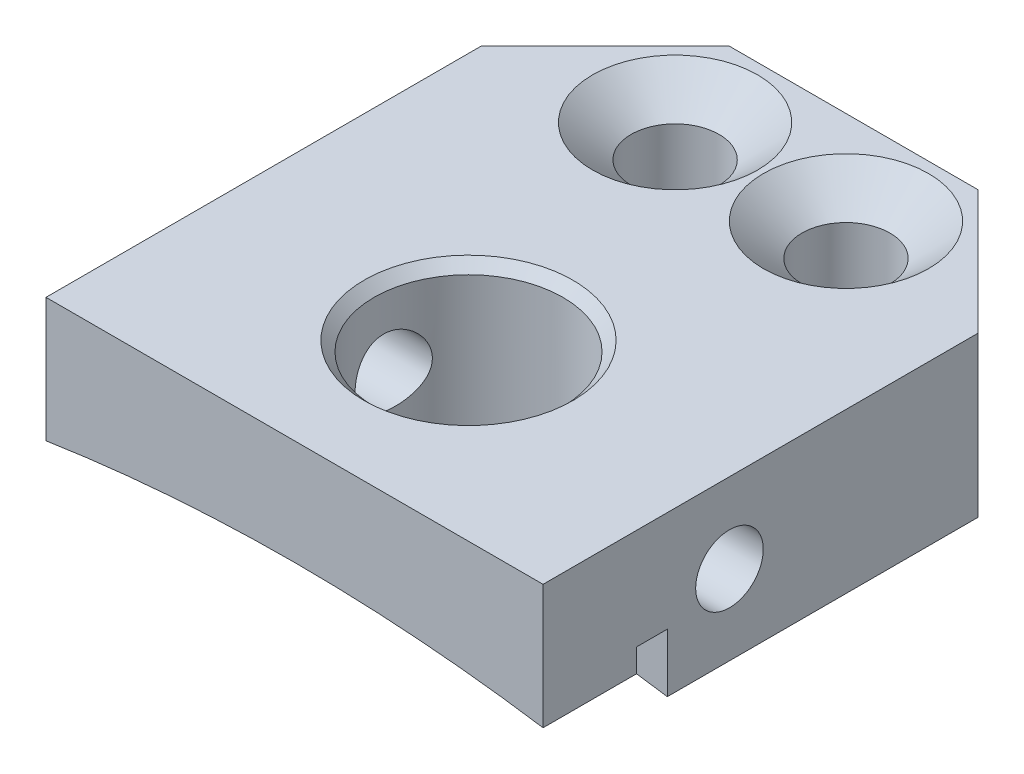
SolidWorks part; units mm, degrees
ref_plane "Front Plane" through (0, 0, 0) normal (0, 0, 1) x (1, 0, 0)
ref_plane "Top Plane" through (0, 0, 0) normal (0, 1, 0) x (1, 0, 0)
ref_plane "Right Plane" through (0, 0, 0) normal (1, 0, 0) x (0, 0, -1)
sketch "Sketch1" plane through (0, 0, 0) normal (0, 1, 0) x (1, 0, 0)
  line L0 (-28.5118, 9.6703) -> (-22.1618, 16.0203)
  line L1 (-22.1618, 16.0203) -> (-9.4618, 16.0203)
  line L2 (-28.5118, 9.6703) -> (-28.5118, -12.5547)
  line L3 (-28.5118, -12.5547) -> (-3.1118, -12.5547)
  line L4 (-3.1118, 9.6703) -> (-3.1118, -12.5547)
  line L5 (-9.4618, 16.0203) -> (-3.1118, 9.6703)
  line L6 (-15.8118, -12.5547) -> (-15.8118, 16.0203) construction
  line L8 (-3.1118, 9.6703) -> (-3.1118, 16.0203) construction
  line L9 (-3.1118, 16.0203) -> (-9.4618, 16.0203) construction
  dimension "D1" = 12.7
  dimension "D2" = 28.575
  dimension "D3" = 25.4
extrude "Boss-Extrude1" add sketch "Sketch1" along normal blind 6.35
sketch "Sketch2" plane through (0, 0, 12.5547) normal (0, 0, 1) x (1, 0, 0)
  circle A0 centre (-15.8118, -82.8523) radius 83.82
  dimension "D1" = 167.64
extrude "Cut-Extrude1" cut sketch "Sketch2" against normal through all both and the other way through all
sketch "Sketch5" plane through (0, 0, -16.0203) normal (0, 0, -1) x (-1, 0, 0)
  line L0 (3.1118, 6.35) -> (3.1118, 0) construction
  line L1 (3.1118, 6.35) -> (3.1118, 0)
  line L4 (28.5118, 6.35) -> (28.5118, 0) construction
  line L5 (28.5118, 6.35) -> (28.5118, 0)
  line L6 (28.5118, -1.7992) -> (28.5118, 0)
  line L7 (3.1118, -1.7992) -> (3.1118, 0)
  line L8 (3.1118, 6.35) -> (28.5118, 6.35)
  arc A0 (3.1118, -1.7992) -> (28.5118, -1.7992) centre (15.8118, -82.8523) cw
  arc A1 (28.5118, 0) -> (3.1118, 0) centre (15.8118, -82.8523) ccw construction
  arc A2 (28.5118, 0) -> (3.1118, 0) centre (15.8118, -82.8523) ccw construction
  dimension "D1" = 82.042
extrude "Boss-Extrude2" add sketch "Sketch5" against normal blind 22.225
chamfer "Chamfer1" distance 6.35 angle 45 2 edges at (-28.5118, 2.2754, -16.0203) (-3.1118, 2.2754, -16.0203)
hole_wizard "CSK for #8 Flat Head Machine Screw (100)1" positions "Sketch3" profile "Sketch4" countersink size "#8" standard "ANSI Inch" end condition through all
sketch "Sketch3" plane through (0, 6.35, 0) normal (0, 1, 0) x (1, 0, 0)
  line L0 (-15.8118, 16.0203) -> (-15.8118, 3.4006) construction
  line L1 (-9.4618, 16.0203) -> (-22.1618, 16.0203) construction
  point P0 (-20.1775, 11.2578)
  point P12 (-11.4462, 11.2578)
  dimension "D1" = 4.7625
  dimension "D2" = 4.3656
sketch "Sketch4" plane through (-20.1775, 6.35, -11.2578) normal (1, 0, 0) x (0, 0, 1)
  line L0 (0, 0) -> (0, 8.1492)
  line L1 (0, 8.1492) -> (2.2479, 8.1492)
  line L2 (2.2479, 8.1492) -> (2.2479, 1.6518)
  line L3 (2.2479, 1.6518) -> (4.2164, 0)
  line L5 (4.2164, 0) -> (0, 0)
  line L6 (-2.2479, 1.6518) -> (-4.2164, 0) construction
  line L11 (0, -6.35) -> (0, 107.95) construction
  dimension "Thru Hole Dia." = 4.4958
  dimension "Thru Hole Depth" = 8.1492
  dimension "Near C'Sink Dia." = 8.4328
  dimension "Near C'Sink Angle" = 100
sketch "Sketch6" plane through (0, 6.35, 0) normal (0, 1, 0) x (1, 0, 0)
  line L0 (-9.4618, 16.0203) -> (-22.1618, 16.0203) construction
  line L1 (-15.8118, -12.5547) -> (-15.8118, 16.0203) construction
  line L2 (-28.5118, -12.5547) -> (-3.1118, -12.5547) construction
  circle A1 centre (-15.8118, -3.6647) radius 1.524
  dimension "D1" = 3.048
  dimension "D2" = 19.685
extrude "Cut-Extrude2" cut sketch "Sketch6" against normal through all
sketch "Sketch7" plane through (-3.1118, 0, 0) normal (1, 0, 0) x (0, 0, -1)
  line L1 (-6.2047, -1.7992) -> (-7.7922, -1.7992)
  line L2 (-6.2047, -1.7992) -> (-6.2047, 1.1906)
  line L3 (-6.2047, 1.1906) -> (-7.7922, 1.1906)
  line L4 (-7.7922, -1.7992) -> (-7.7922, 1.1906)
  line L5 (-6.2047, -1.7992) -> (9.6703, -1.7992) construction
  line L6 (-12.5547, 0) -> (-6.2047, 0) construction
  line L7 (-6.2047, 0) -> (-6.2047, -1.7992) construction
  dimension "D1" = 1.5875
  dimension "D2" = 1.1906
extrude "Cut-Extrude3" cut sketch "Sketch7" against normal through all
sketch "Sketch8" plane through (0, 6.35, 0) normal (0, 1, 0) x (1, 0, 0)
  circle A0 centre (-15.8118, -3.6647) radius 4.826
  dimension "D1" = 9.652
extrude "Cut-Extrude4" cut sketch "Sketch8" against normal through all
chamfer "Chamfer2" distance 0.508 angle 45 1 edges at (-15.8118, 6.35, 8.4907)
hole_wizard "#8-32 Tapped Hole1" positions "Sketch9" profile "Sketch10" tap size "#8-32" standard "ANSI Inch" end condition through all
sketch "Sketch9" plane through (-28.5118, 0, 0) normal (-1, 0, 0) x (0, 0, 1)
  line L0 (8.4907, 5.842) -> (-1.1613, 5.842) construction
  line L1 (8.4907, 5.842) -> (-1.1613, 5.842)
  line L2 (3.0297, 6.35) -> (3.0297, -1.7992) construction
  line L3 (-9.6703, 6.35) -> (12.5547, 6.35) construction
  line L4 (6.2047, -1.7992) -> (-9.6703, -1.7992) construction
  point P0 (3.0297, 2.2754)
  point P13 (3.6647, 5.842)
  point P14 (0, 0)
  dimension "D1" = 0.635
sketch "Sketch10" plane through (-28.5118, 2.2754, 3.0297) normal (0, 1, 0) x (0, 0, 1)
  line L0 (0, 0) -> (0, 25.4)
  line L1 (0, 25.4) -> (1.7272, 25.4)
  line L2 (1.7272, 25.4) -> (1.7272, 0)
  line L5 (1.7272, 0) -> (0, 0)
  line L11 (0, -6.35) -> (0, 107.95) construction
  dimension "Thru Tap Drill Dia." = 3.4544
  dimension "Thru Tap Drill Depth" = 25.4
cosmetic thread "Hole Thread1" parameters "D2"=4.1656
